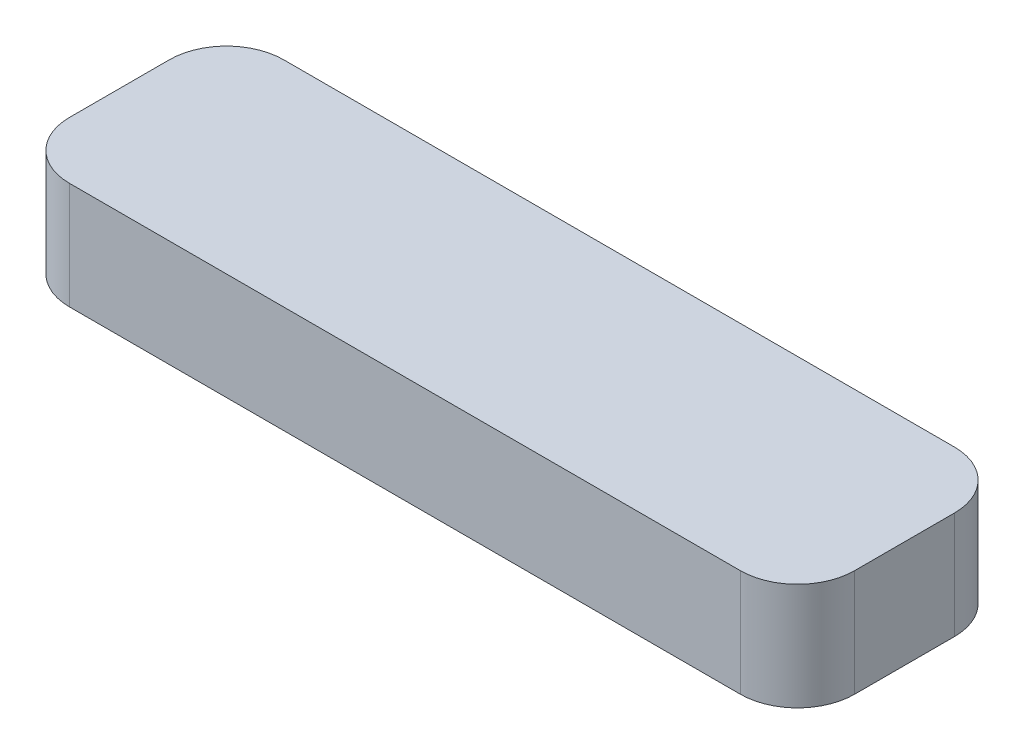
SolidWorks part; units mm, degrees
ref_plane "Front Plane" through (0, 0, 0) normal (0, 0, 1) x (1, 0, 0)
ref_plane "Top Plane" through (0, 0, 0) normal (0, 1, 0) x (1, 0, 0)
ref_plane "Right Plane" through (0, 0, 0) normal (1, 0, 0) x (0, 0, -1)
sketch "Sketch1" plane through (0, 0, 0) normal (0, 1, 0) x (1, 0, 0)
  line L1 (-46.7568, 18.1081) -> (63.2432, 18.1081)
  line L2 (-46.7568, 18.1081) -> (-46.7568, -11.8919)
  line L3 (-46.7568, -11.8919) -> (63.2432, -11.8919)
  line L4 (63.2432, 18.1081) -> (63.2432, -11.8919)
  dimension "D1" = 110
  dimension "D2" = 30
extrude "Boss-Extrude1" add sketch "Sketch1" along normal blind 15
fillet "Fillet2" radius 8 4 edges at (63.2432, 7.5, -18.1081) (63.2432, 7.5, 11.8919) (-46.7568, 7.5, -18.1081) (-46.7568, 7.5, 11.8919)
sketch "Sketch3" plane through (0, 15, 0) normal (0, 1, 0) x (1, 0, 0)
  line L0 (55.2432, 18.1081) -> (-38.7568, 18.1081) construction
  line L1 (-34.6791, 9.6081) -> (-11.6791, 9.6081)
  line L2 (-34.6791, 9.6081) -> (-34.6791, -3.3919)
  line L3 (-34.6791, -3.3919) -> (-11.6791, -3.3919)
  line L4 (-11.6791, 9.6081) -> (-11.6791, -3.3919)
  point P4 (-23.1791, 9.6081)
  dimension "D1" = 23
  dimension "D2" = 13
  dimension "D3" = 8.5
sketch "Sketch4" plane through (0, 15, 0) normal (0, 1, 0) x (1, 0, 0)
  line L0 (55.2432, 18.1081) -> (-38.7568, 18.1081) construction
  line L1 (-34.6791, 9.6081) -> (-34.6791, -3.3919) construction
  circle A0 centre (-27.9291, 3.1081) radius 6.5
  circle A1 centre (-36.9291, 3.1081) radius 1
  dimension "D1" = 15
  dimension "D2" = 6.75
  dimension "D3" = 2.5
